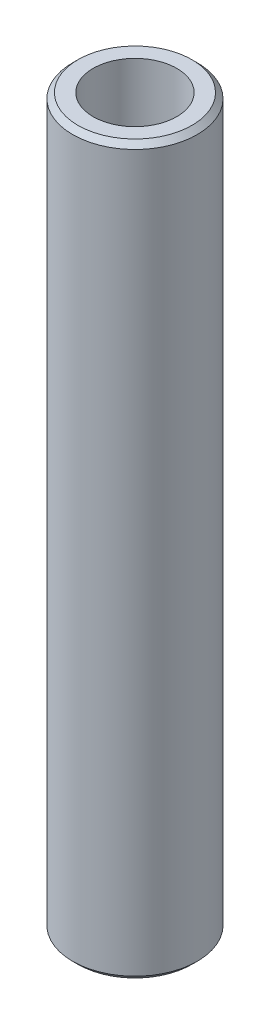
SolidWorks part; units mm, degrees
ref_plane "Front Plane" through (0, 0, 0) normal (0, 0, 1) x (1, 0, 0)
ref_plane "Top Plane" through (0, 0, 0) normal (0, 1, 0) x (1, 0, 0)
ref_plane "Right Plane" through (0, 0, 0) normal (1, 0, 0) x (0, 0, -1)
sketch "Sketch1" plane through (0, 0, 0) normal (0, 1, 0) x (1, 0, 0)
  circle A0 centre (0, 0) radius 42.5
  dimension "SHAFT_OD" = 85
extrude "Boss-Extrude1" add sketch "Sketch1" along normal blind 495.7344
sketch "Sketch2" plane through (0, 0, 0) normal (0, 1, 0) x (1, 0, 0)
  circle A0 centre (0, 0) radius 28.5581
  dimension "BORE_D" = 57.1162
extrude "Cut-Extrude1" cut sketch "Sketch2" along normal through all
chamfer "Chamfer1" distance 3.6266 angle 45 2 edges at (0, 495.7344, 42.5) (0, 0, 42.5)
